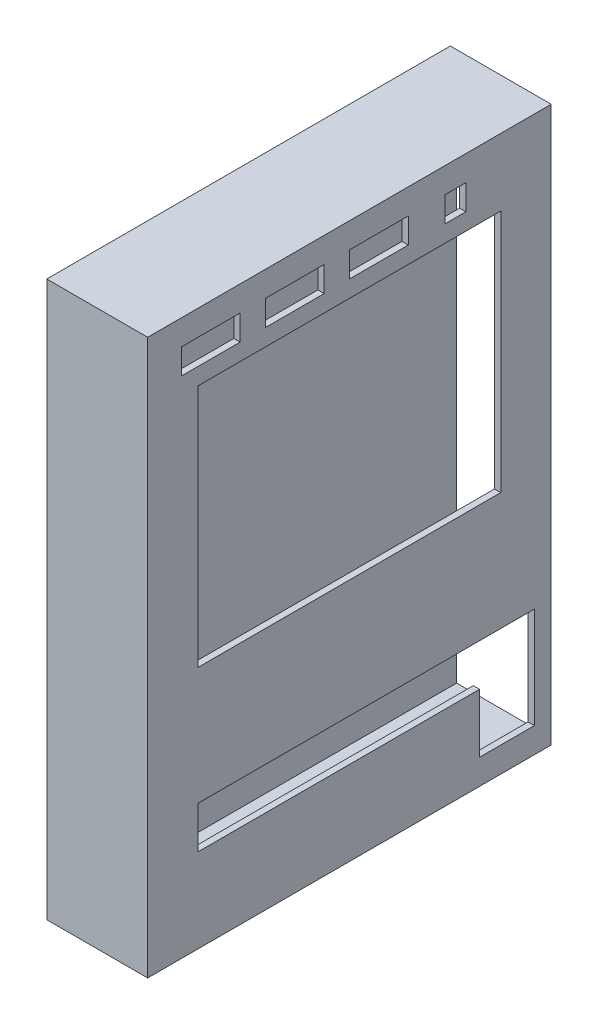
SolidWorks part; units mm, degrees
ref_plane "Front Plane" through (0, 0, 0) normal (0, 0, 1) x (1, 0, 0)
ref_plane "Top Plane" through (0, 0, 0) normal (0, 1, 0) x (1, 0, 0)
ref_plane "Right Plane" through (0, 0, 0) normal (1, 0, 0) x (0, 0, -1)
sketch "Sketch1" plane through (0, 0, 0) normal (1, 0, 0) x (0, 0, -1)
  line L0 (-304.8, 0) -> (304.8, 0) construction
  line L3 (-304.8, 0) -> (304.8, 0)
  line L4 (-304.8, 0) -> (-304.8, 838.2)
  line L5 (-304.8, 838.2) -> (304.8, 838.2)
  line L6 (304.8, 0) -> (304.8, 838.2)
  point P4 (0, 0)
  dimension "D1" = 609.6
  dimension "D2" = 838.2
extrude "OuterBodie" add sketch "Sketch1" against normal blind 152.4
shell "Shell1" thickness 9.525 removed face at (-76.2, 419.1, -304.8)
sketch "Sketch2" plane through (0, 0, 0) normal (1, 0, 0) x (0, 0, -1)
  line L0 (0, 0) -> (0, 342.9) construction
  line L4 (-228.6, 368.3) -> (228.6, 368.3)
  line L6 (-228.6, 736.6) -> (228.6, 736.6)
  line L9 (304.8, 838.2) -> (-304.8, 838.2) construction
  line L10 (-228.6, 736.6) -> (-228.6, 368.3)
  line L11 (228.6, 736.6) -> (228.6, 368.3)
  line L12 (-304.8, 838.2) -> (-304.8, 0) construction
  line L13 (-304.8, 0) -> (304.8, 0) construction
  dimension "D1" = 368.3
  dimension "D2" = 101.6
  dimension "D3" = 457.2
  dimension "D4" = 76.2
  dimension "D5" = 368.3
sketch "Sketch3" plane through (0, 0, 0) normal (1, 0, 0) x (0, 0, -1)
  line L0 (0, 0) -> (0, 127) construction
  line L1 (0, 0) -> (0, 342.9) construction
  line L2 (-228.6, 127) -> (228.6, 127)
  line L3 (-228.6, 127) -> (-228.6, 190.5)
  line L4 (-228.6, 190.5) -> (228.6, 190.5)
  line L9 (228.6, 190.5) -> (228.6, 127)
  point P8 (0, 127)
  dimension "D1" = 127
  dimension "D2" = 457.2
  dimension "D3" = 63.5
extrude "Wire duct" cut sketch "Sketch3" against normal up to surface (9.525 mm away) up to face at (-9.525, 419.1, -4.7625)
extrude "Display cutout" cut sketch "Sketch2" against normal up to surface (9.525 mm away) up to face at (-9.525, 158.75, 0)
sketch "Sketch5" plane through (0, 0, 0) normal (1, 0, 0) x (0, 0, -1)
  line L0 (-304.8, 762) -> (304.8, 762) construction
  line L1 (-304.8, 838.2) -> (-304.8, 0) construction
  line L2 (304.8, 0) -> (304.8, 838.2) construction
  line L3 (304.8, 838.2) -> (-304.8, 838.2) construction
  line L5 (-254, 762) -> (-165.1, 762)
  line L6 (-254, 762) -> (-254, 800.1)
  line L7 (-254, 800.1) -> (-165.1, 800.1)
  line L8 (-165.1, 762) -> (-165.1, 800.1)
  line L9 (-127, 762) -> (-127, 800.1)
  line L10 (-127, 762) -> (-38.1, 762)
  line L11 (-38.1, 762) -> (-38.1, 800.1)
  line L12 (-127, 800.1) -> (-38.1, 800.1)
  line L13 (0, 762) -> (0, 800.1)
  line L14 (0, 762) -> (88.9, 762)
  line L15 (88.9, 762) -> (88.9, 800.1)
  line L16 (0, 800.1) -> (88.9, 800.1)
  line L18 (144.1513, 762) -> (175.9013, 762)
  line L19 (144.1513, 762) -> (144.1513, 800.1)
  line L20 (144.1513, 800.1) -> (175.9013, 800.1)
  line L21 (175.9013, 762) -> (175.9013, 800.1)
  dimension "D1" = 76.2
  dimension "D2" = 50.8
  dimension "D3" = 88.9
  dimension "D4" = 38.1
  dimension "D6" = 38.1
  dimension "D7" = 31.75
  dimension "D5" = 3
extrude "Game Display" cut sketch "Sketch5" against normal up to surface (9.525 mm away) up to face at (-9.525, 552.45, 0)
sketch "Sketch6" plane through (0, 0, 0) normal (1, 0, 0) x (0, 0, -1)
  line L6 (228.6, 190.5) -> (-228.6, 190.5) construction
  line L7 (304.8, 0) -> (304.8, 838.2) construction
  line L8 (196.5766, 190.5) -> (279.4, 190.5)
  line L9 (196.5766, 190.5) -> (196.5766, 38.1)
  line L10 (196.5766, 38.1) -> (279.4, 38.1)
  line L11 (279.4, 190.5) -> (279.4, 38.1)
  line L12 (-304.8, 0) -> (304.8, 0) construction
  dimension "D1" = 25.4
  dimension "D2" = 108.2234
  dimension "D3" = 38.1
extrude "Cut-Extrude1" cut sketch "Sketch6" against normal up to surface (9.525 mm away) up to face at (-9.525, 781.05, 209.55)
